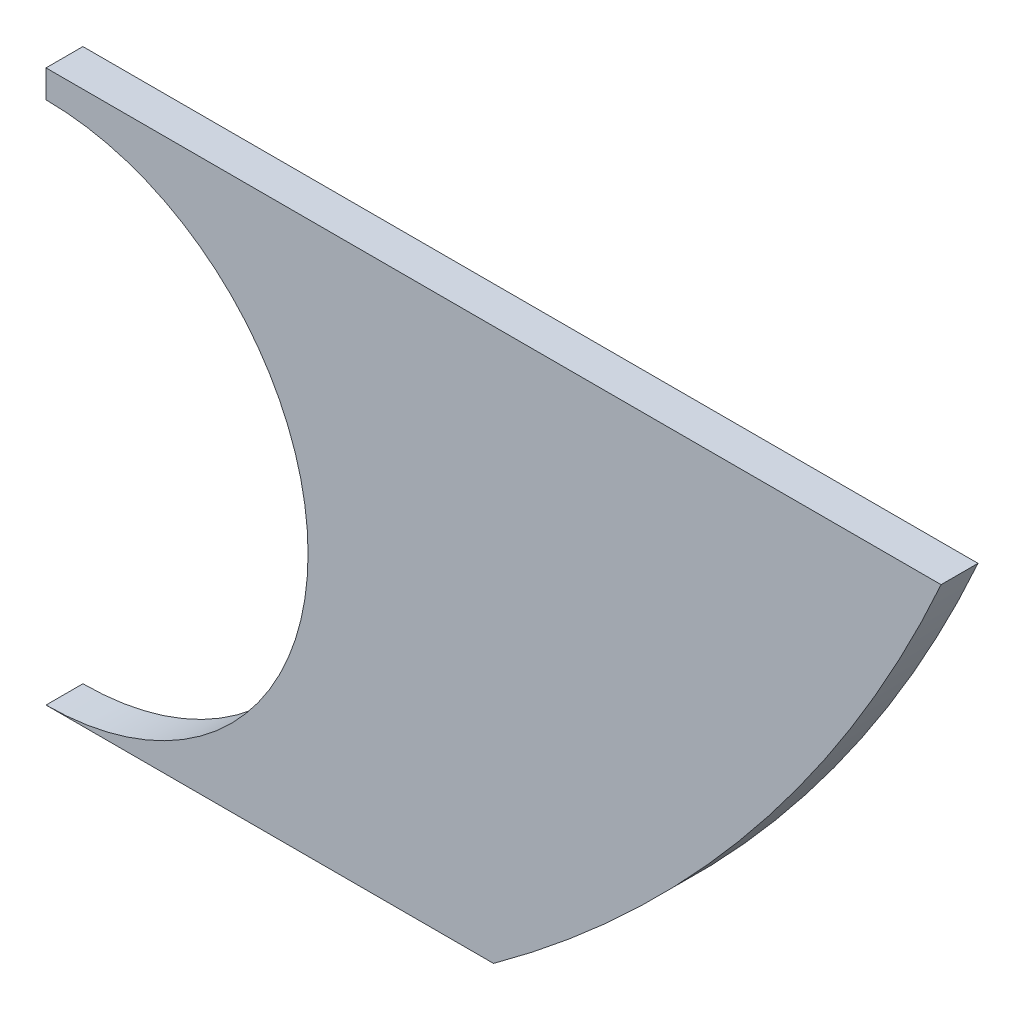
SolidWorks part; units mm, degrees
ref_plane "Front Plane" through (0, 0, 0) normal (0, 0, 1) x (1, 0, 0)
ref_plane "Top Plane" through (0, 0, 0) normal (0, 1, 0) x (1, 0, 0)
ref_plane "Right Plane" through (0, 0, 0) normal (1, 0, 0) x (0, 0, -1)
sketch "Sketch1" plane through (0, 0, 0) normal (0, 0, 1) x (1, 0, 0)
  circle A0 centre (0, 0) radius 19.939
  dimension "D1" = 39.878
extrude "circle extrude" add sketch "Sketch1" along normal blind 2.54
sketch "Sketch3" plane through (0, 0, 0) normal (1, 0, 0) x (0, 0, -1)
  line L0 (0, 21.9329) -> (0, -21.9329) construction
  line L1 (-2.54, 19.939) -> (0, 19.939)
  line L2 (-2.54, 19.939) -> (-2.54, -19.939)
  line L3 (-2.54, -19.939) -> (0, -19.939)
  line L4 (0, 19.939) -> (0, -19.939)
  line L5 (-2.54, -19.939) -> (0, -19.939) construction
extrude "rectangle extrude" add sketch "Sketch3" along normal blind 63.5
sketch "Sketch2" plane through (0, 0, 2.54) normal (0, 0, 1) x (1, 0, 0)
  circle A0 centre (0, 0) radius 18.034
  dimension "D1" = 36.068
extrude "cricle cut" cut sketch "Sketch2" against normal blind 2.54
sketch "Sketch4" plane through (0, 0, 2.54) normal (0, 0, 1) x (1, 0, 0)
  line L0 (63.5, 19.939) -> (63.5, -19.939) construction
  line L1 (0, 19.939) -> (61.595, 19.939)
  line L2 (0, 19.939) -> (0, -18.034)
  line L3 (0, -18.034) -> (61.595, -18.034)
  line L4 (61.595, 19.939) -> (61.595, -18.034)
  line L5 (63.5, -19.939) -> (0, -19.939) construction
  point P12 (0, 0)
  dimension "D1" = 1.905
  dimension "D2" = 1.905
extrude "frame cut" cut sketch "Sketch4" against normal through all flip side to cut
sketch "Sketch8" plane through (0, 0, 2.54) normal (0, 0, 1) x (1, 0, 0)
  line L0 (0, -18.034) -> (61.595, -18.034) construction
  line L1 (61.595, 19.939) -> (61.595, -18.034)
  line L2 (61.595, -18.034) -> (30.7975, -18.034)
  arc A0 (30.7975, -18.034) -> (61.595, 19.939) centre (-24.6623, 58.4214) ccw
  dimension "D1" = 94.4522
extrude "Cut-Extrude4" cut sketch "Sketch8" against normal through all
